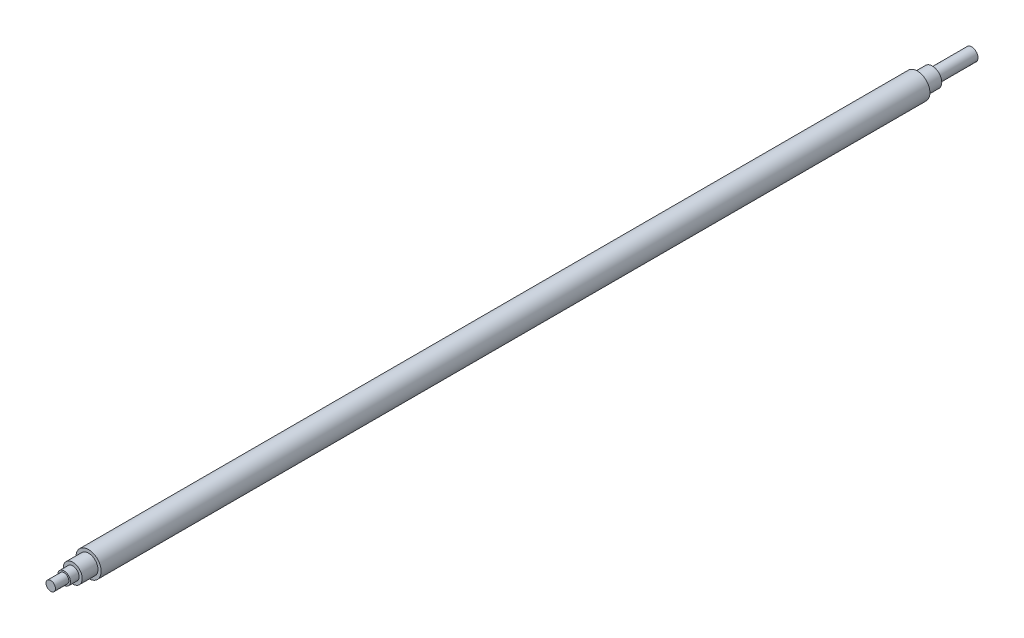
SolidWorks part; units mm, degrees
ref_plane "Piano frontale" through (0, 0, 0) normal (0, 0, 1) x (1, 0, 0)
ref_plane "Piano superiore" through (0, 0, 0) normal (0, 1, 0) x (1, 0, 0)
ref_plane "Piano destro" through (0, 0, 0) normal (1, 0, 0) x (0, 0, -1)
sketch "Schizzo2" plane through (0, 0, 0) normal (1, 0, 0) x (0, 0, -1)
  line L0 (8.5, 0) -> (8.5, 3)
  line L1 (8.5, 3) -> (17, 3)
  line L2 (17, 3) -> (17, 4)
  line L3 (17, 4) -> (22.5, 4)
  line L4 (22.5, 4) -> (22.5, 6)
  line L5 (22.5, 6) -> (32.5, 6)
  line L6 (32.5, 6) -> (32.5, 8)
  line L7 (32.5, 8) -> (558.5, 8)
  line L8 (558.5, 8) -> (558.5, 6)
  line L9 (558.5, 6) -> (568, 6)
  line L10 (568, 6) -> (568, 4)
  line L11 (593, 0) -> (8.5, 0)
  line L14 (593, 0) -> (593, 4)
  line L15 (0, 0) -> (351.0218, 0) construction
  line L18 (568, 4) -> (593, 4)
  point P33 (0, 0)
  dimension "D2" = 6
  dimension "D3" = 8
  dimension "D4" = 12
  dimension "D5" = 16
  dimension "D6" = 12
  dimension "D7" = 8
  dimension "D8" = 8.5
  dimension "D9" = 5.5
  dimension "D10" = 10
  dimension "D11" = 526
  dimension "D12" = 9.5
  dimension "D13" = 25
  dimension "D14" = 584.5
revolve "Rivoluzione2" add sketch "Schizzo2" angle 360 about L15
